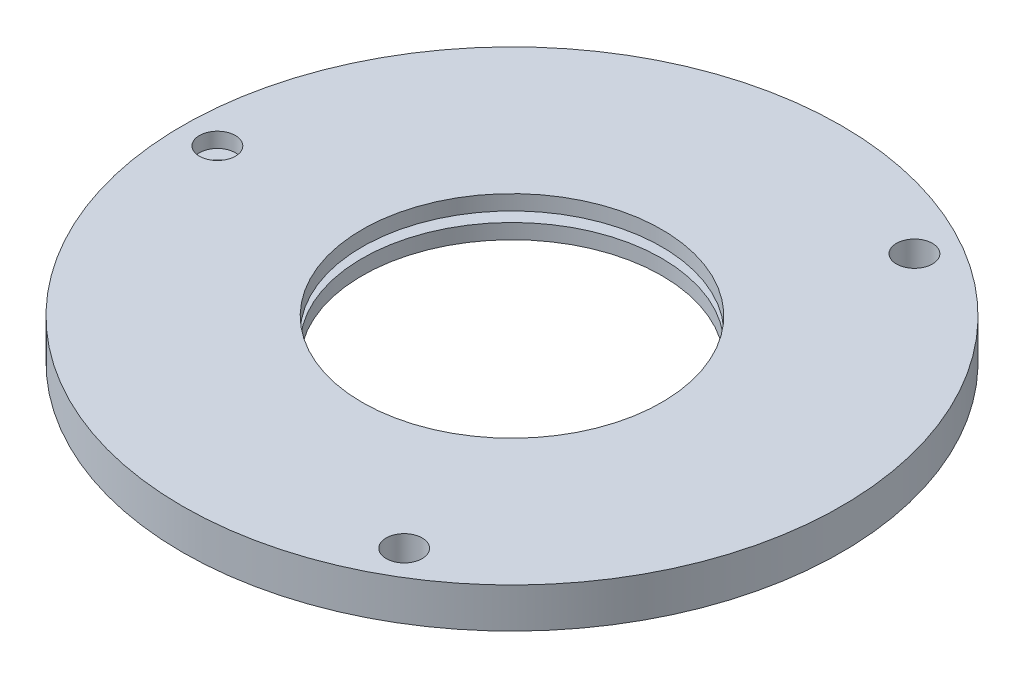
SolidWorks part; units mm, degrees
material "PEI"
ref_plane "Front Plane" through (0, 0, 0) normal (0, 0, 1) x (1, 0, 0)
ref_plane "Top Plane" through (0, 0, 0) normal (0, 1, 0) x (1, 0, 0)
ref_plane "Right Plane" through (0, 0, 0) normal (1, 0, 0) x (0, 0, -1)
sketch "Sketch1" plane through (0, 0, 0) normal (0, 1, 0) x (1, 0, 0)
  circle A0 centre (0, 0) radius 33
  circle A1 centre (-29.5, 0) radius 1.5
  circle A2 centre (0, 0) radius 29.5 construction
  circle A3 centre (14.75, 25.5477) radius 1.5
  circle A4 centre (14.75, -25.5477) radius 1.5
  point P12 (0, 0)
  point P15 (0, 0)
  dimension "D1" = 66
  dimension "D2" = 3.5
  dimension "D3" = 3
  dimension "D5" = 29.5
  dimension "D4" = 3
extrude "Boss-Extrude1" add sketch "Sketch1" along normal blind 4
hole_wizard "CSK for M3 Flat Head Machine Screw1" positions "Sketch2" profile "Sketch3" countersink size "M3" standard "ANSI Metric" end condition through all
sketch "Sketch2" plane through (0, 0, 0) normal (0, -1, 0) x (-1, 0, 0)
  circle A0 centre (-14.75, -25.5477) radius 1.5 construction
  circle A1 centre (-14.75, 25.5477) radius 1.5 construction
  point P0 (-14.75, -25.5477)
  point P3 (29.5, 0)
  point P6 (-14.75, 25.5477)
sketch "Sketch3" plane through (14.75, 0, 25.5477) normal (1, 0, 0) x (0, 0, -1)
  line L0 (0, 0) -> (0, 4)
  line L1 (0, 4) -> (1.8, 4)
  line L2 (1.8, 4) -> (1.8, 1.35)
  line L3 (1.8, 1.35) -> (3.15, 0)
  line L5 (3.15, 0) -> (0, 0)
  line L6 (-1.8, 1.35) -> (-3.15, 0) construction
  line L11 (0, -6.35) -> (0, 107.95) construction
  dimension "Thru Hole Dia." = 3.6
  dimension "Thru Hole Depth" = 4
  dimension "Near C'Sink Dia." = 6.3
  dimension "Near C'Sink Angle" = 90
sketch "Croquis1" plane through (0, 0, 0) normal (0, -1, 0) x (1, 0, 0)
  circle A0 centre (0, 0) radius 15
  dimension "D1" = 30
extrude "Cortar-Extruir1" cut sketch "Croquis1" against normal up to next
ref_axis "Eje1" through (0, 4, 0) along (0, -1, 0)
ref_plane "Plano1" through (-33, 0, 0) normal (-1, 0, 0) x (0, 0, 1)
sketch "Croquis2" plane through (-33, 0, 0) normal (-1, 0, 0) x (0, 0, 1)
  line L0 (0, 0) -> (0, 4) construction
  line L1 (0, 4) -> (0, 0) construction
  line L3 (-20, 2.5) -> (20, 2.5)
  line L4 (-20, 2.5) -> (-20, 1.5)
  line L5 (-20, 1.5) -> (20, 1.5)
  line L6 (20, 2.5) -> (20, 1.5)
  line L7 (-20, 2.5) -> (20, 1.5) construction
  line L8 (-20, 1.5) -> (20, 2.5) construction
  line L10 (-33, 0) -> (33, 0) construction
  line L11 (33, 4) -> (-33, 4) construction
  point P5 (0, 2)
  dimension "D1" = 40
  dimension "D2" = 1
  dimension "D3" = 1.5
  dimension "D4" = 1.5
extrude "Cortar-Extruir2" cut sketch "Croquis2" against normal blind 50
